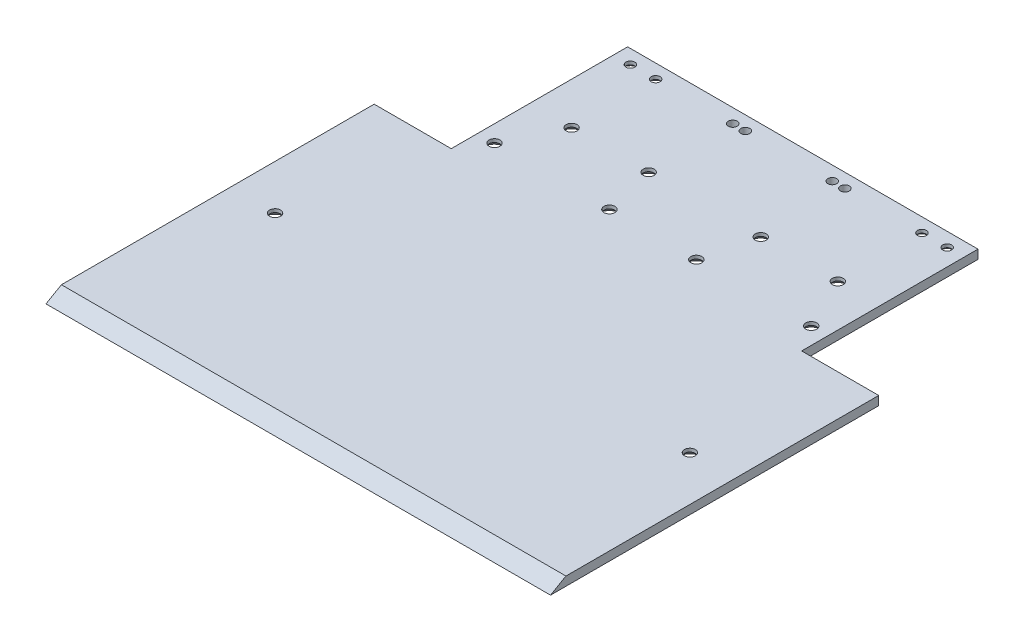
SolidWorks part; units mm, degrees
ref_plane "Alzado" through (0, 0, 0) normal (0, 0, 1) x (1, 0, 0)
ref_plane "Planta" through (0, 0, 0) normal (0, 1, 0) x (1, 0, 0)
ref_plane "Vista lateral" through (0, 0, 0) normal (1, 0, 0) x (0, 0, -1)
sketch "Croquis1" plane through (0, 0, 0) normal (0, 1, 0) x (1, 0, 0)
  line L0 (-62.5, 90) -> (-62.5, 27.08)
  line L1 (90, -90) -> (-90, -90)
  line L2 (90, -90) -> (90, 27.08)
  line L3 (62.5, 90) -> (-62.5, 90)
  line L4 (-90, -90) -> (-90, 27.08)
  line L5 (90, -90) -> (-62.5, 62.5) construction
  line L6 (62.5, 62.5) -> (-90, -90) construction
  line L7 (-62.5, 27.08) -> (-90, 27.08)
  line L8 (0, 90) -> (0, -90) construction
  line L9 (62.5, 27.08) -> (90, 27.08)
  line L10 (62.5, 90) -> (62.5, 27.08)
  point P0 (0, 0)
  dimension "D1" = 125
  dimension "D2" = 180
  dimension "D3" = 27.5
  dimension "D4" = 62.92
  dimension "D5" = 27.5
extrude "Saliente-Extruir1" add sketch "Croquis1" along normal blind 3.17
sketch "Croquis2" plane through (-90, 0, 0) normal (-1, 0, 0) x (0, 0, 1)
  line L0 (90, 0) -> (84.5094, 3.17)
  line L1 (-27.08, 3.17) -> (90, 3.17) construction
  line L2 (84.5094, 3.17) -> (90, 3.17)
  line L3 (90, 3.17) -> (90, 0)
  dimension "D1" = 60
extrude "Cortar-Extruir1" cut sketch "Croquis2" against normal up to next
sketch "Croquis3" plane through (0, 3.17, 0) normal (0, 1, 0) x (1, 0, 0)
  circle A0 centre (74, -24.2793) radius 1.585
extrude "Cortar-Extruir2" cut sketch "Croquis3" against normal up to next
mirror "Simetría1" about plane through (0, 0, 0) normal (1, 0, 0) of "Cortar-Extruir2"
sketch "Croquis4" plane through (0, 3.17, 0) normal (0, 1, 0) x (1, 0, 0)
  circle A0 centre (-56.5, 36.5006) radius 1.585
  circle A1 centre (-15.5, 36.5006) radius 1.585
  circle A2 centre (-15.5, 85.0006) radius 1.585
  circle A3 centre (-56.5, 85.0006) radius 1.585
extrude "Cortar-Extruir3" cut sketch "Croquis4" against normal up to next
sketch "Croquis6" plane through (0, 3.17, 0) normal (0, 1, 0) x (1, 0, 0)
  circle A0 centre (56.5, 85.0006) radius 1.585
  circle A1 centre (15.5, 85.0006) radius 1.585
  circle A2 centre (15.5, 36.5006) radius 1.585
  circle A3 centre (56.5, 36.5006) radius 1.585
extrude "Cortar-Extruir4" cut sketch "Croquis6" against normal up to next
sketch "Croquis7" plane through (0, 3.17, 0) normal (0, 1, 0) x (1, 0, 0)
  circle A0 centre (-20, 85.0006) radius 1.585
  circle A1 centre (-47.5, 85.0006) radius 1.585
  circle A2 centre (-47.5, 55.0006) radius 1.585
  circle A3 centre (-20, 55.0006) radius 1.585
extrude "Cortar-Extruir5" cut sketch "Croquis7" against normal up to next
mirror "Simetría2" about plane through (0, 0, 0) normal (1, 0, 0) of "Cortar-Extruir5"
sketch "Croquis15" plane through (0, 0, 0) normal (0, -1, 0) x (-1, 0, 0)
  circle A0 centre (20, 55.0006) radius 4
  circle A1 centre (15.5, 36.5006) radius 4
  circle A2 centre (56.5, 36.5006) radius 4
  circle A3 centre (47.5, 55.0006) radius 4
  circle A4 centre (56.5, 85.0006) radius 4
  circle A5 centre (47.5, 85.0006) radius 4
  circle A8 centre (74, -24.2793) radius 4
  dimension "D1" = 8
  dimension "D3" = 8
  dimension "D4" = 8
  dimension "D5" = 8
  dimension "D6" = 8
  dimension "D7" = 8
  dimension "D8" = 8
extrude "Cortar-Extruir6" cut sketch "Croquis15" against normal blind 2 draft 50.5
mirror "Simetría3" about plane through (0, 0, 0) normal (1, 0, 0) of "Cortar-Extruir6"
sketch "Croquis13" plane through (0, 0, 0) normal (0, -1, 0) x (-1, 0, 0)
  point P0 (-74, -24.2793)
  point P3 (-56.5, 36.5006)
  point P6 (-47.5, 55.0006)
  point P9 (-20, 55.0006)
  point P12 (-15.5, 36.5006)
  point P15 (15.5, 36.5006)
  point P18 (20, 55.0006)
  point P21 (47.5, 55.0006)
  point P24 (56.5, 36.5006)
  point P27 (74, -24.2793)
hole_wizard "Avellanado para tornillo con cabeza avellanada en cruz de M3.51" positions "Croquis13" profile "Croquis14" countersink size "M3.5" standard "AS" end condition through all
sketch "Croquis14" plane through (74, 0, 24.2793) normal (1, 0, 0) x (0, 0, -1)
  line L0 (0, 0) -> (0, 3.17)
  line L1 (0, 3.17) -> (1.95, 3.17)
  line L2 (1.95, 3.17) -> (1.95, 1.9797)
  line L3 (1.95, 1.9797) -> (4, 0)
  line L5 (4, 0) -> (0, 0)
  line L6 (-1.95, 1.9797) -> (-4, 0) construction
  line L11 (0, -6.35) -> (0, 107.95) construction
  dimension "Diámetro de taladro hasta el siguiente" = 3.9
  dimension "Profundidad de taladro hasta el siguiente" = 3.17
  dimension "Diámetro de avellanado cercano" = 8
  dimension "Ángulo de avellanado cercano" = 92
